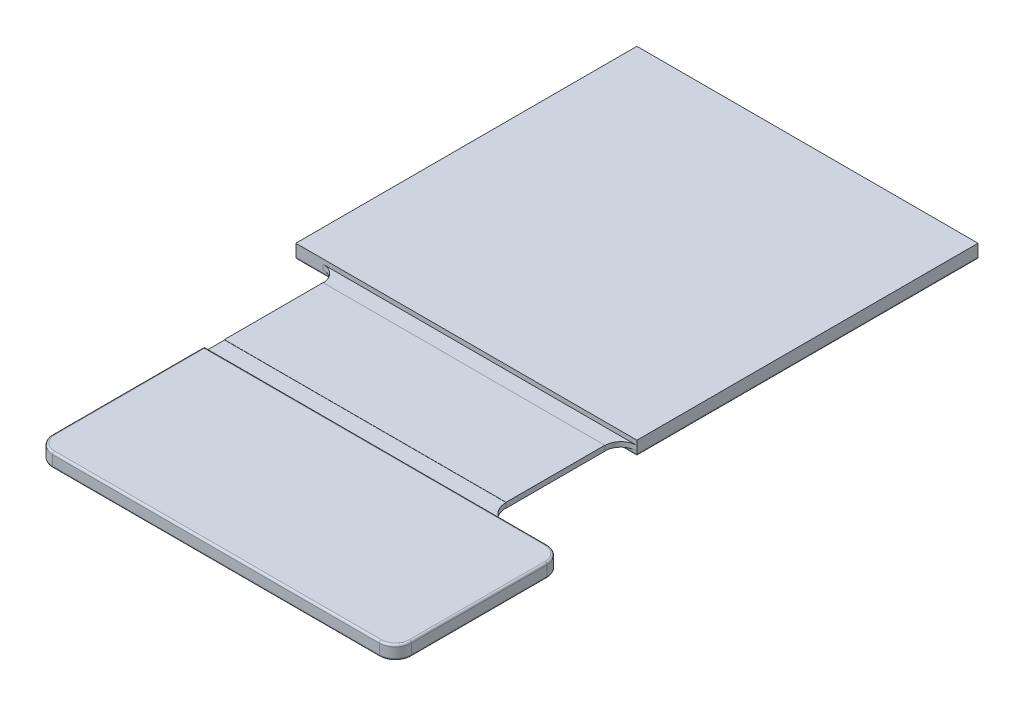
SolidWorks part; units mm, degrees
ref_plane "Front Plane" through (0, 0, 0) normal (0, 0, 1) x (1, 0, 0)
ref_plane "Top Plane" through (0, 0, 0) normal (0, 1, 0) x (1, 0, 0)
ref_plane "Right Plane" through (0, 0, 0) normal (1, 0, 0) x (0, 0, -1)
sketch "Sketch1" plane through (0, 0, 0) normal (0, 1, 0) x (1, 0, 0)
  line L1 (-4.25, 4.25) -> (4.25, 4.25) construction
  line L2 (-4.25, 4.25) -> (-4.25, -4.25) construction
  line L3 (-4.25, -4.25) -> (4.25, -4.25) construction
  line L4 (4.25, 4.25) -> (4.25, -4.25) construction
  line L5 (-4.25, 4.25) -> (4.25, -4.25) construction
  line L6 (-4.25, -4.25) -> (4.25, 4.25) construction
  line L7 (-12.5, 9.462) -> (12.5, 9.462) construction
  line L8 (-12.5, 9.462) -> (-12.5, -14.4) construction
  line L9 (-12.5, -14.4) -> (12.5, -14.4) construction
  line L10 (12.5, 9.462) -> (12.5, -14.4) construction
  line L11 (-2.27, -8.71) -> (4.87, -8.71) construction
  line L12 (-2.27, -8.71) -> (-2.27, -10.69) construction
  line L13 (-2.27, -10.69) -> (4.87, -10.69) construction
  line L14 (4.87, -8.71) -> (4.87, -10.69) construction
  line L15 (-2.27, -8.71) -> (4.87, -10.69) construction
  line L16 (-2.27, -10.69) -> (4.87, -8.71) construction
  point P0 (0, 0)
  point P10 (1.3, -9.7)
  dimension "D1" = 8.5
  dimension "D2" = 23.862
  dimension "D3" = 25
  dimension "D4" = 12.5
  dimension "D5" = 9.462
  dimension "D6" = 13.8
  dimension "D7" = 4.7
  dimension "D8" = 7.14
  dimension "D9" = 1.98
sketch "Sketch3" plane through (0, 0, 0) normal (0, 1, 0) x (1, 0, 0)
  line L0 (-4.25, 4.25) -> (4.25, 4.25) construction
  line L1 (-4.25, -4.25) -> (4.25, -4.25) construction
  line L2 (-4.25, 4.25) -> (-4.25, -4.25) construction
  line L3 (4.25, 4.25) -> (4.25, -4.25) construction
  line L4 (-4.25, -4.25) -> (-3.17, -4.25)
  line L5 (-4.25, 4.25) -> (-4.25, -4.25)
  line L6 (4.25, 4.25) -> (4.25, -4.25)
  line L7 (-4.25, 4.25) -> (4.25, 4.25)
  line L8 (4.87, -8.71) -> (4.87, -10.69) construction
  line L9 (3.85, -7.61) -> (5.77, -7.61)
  line L11 (-3.17, -11.79) -> (5.77, -11.79)
  line L12 (5.77, -7.61) -> (5.77, -11.79)
  line L13 (-2.27, -10.69) -> (4.87, -10.69) construction
  line L15 (-2.27, -8.71) -> (4.87, -8.71) construction
  line L18 (-3.17, -4.25) -> (-3.17, -11.79)
  line L19 (-2.27, -8.71) -> (-2.27, -10.69) construction
  line L20 (3.85, -4.25) -> (3.85, -7.61)
  line L21 (3.85, -4.25) -> (4.25, -4.25)
  dimension "D1" = 0.9
  dimension "D2" = 1.1
  dimension "D3" = 0.9
  dimension "D4" = 1.1
  dimension "D5" = 7.02
extrude "Boss-Extrude1" add sketch "Sketch3" along normal blind 0.35
fillet "Fillet1" radius 0.4 5 edges at (3.85, 0.175, 4.25) (-3.17, 0.175, 4.25) (5.77, 0.175, 7.61) (5.77, 0.175, 11.79) (-3.17, 0.175, 11.79)
fillet "Fillet2" radius 0.5 1 edges at (3.85, 0.175, 7.61)
sketch "Sketch4" plane through (0, 0.35, 0) normal (0, 1, 0) x (1, 0, 0)
  line L0 (-4.25, -4.25) -> (4.25, -4.25)
  line L1 (4.25, -4.25) -> (4.25, -7.61)
  line L2 (5.37, -7.61) -> (4.35, -7.61) construction
  line L3 (4.25, -7.61) -> (-4.25, -7.61)
  line L4 (-4.25, -7.61) -> (-4.25, -4.25)
extrude "Cut-Extrude1" cut sketch "Sketch4" against normal blind 0.115
sketch "Sketch5" plane through (0, 0, 0) normal (0, -1, 0) x (1, 0, 0)
  line L0 (-4.25, 7.61) -> (-4.25, 4.25) construction
  line L1 (4.25, 7.61) -> (-4.25, 7.61) construction
  line L2 (-4.25, 4.25) -> (4.25, 4.25) construction
  line L3 (4.25, 4.25) -> (4.25, 7.61) construction
  line L4 (-4.25, 7.61) -> (-4.25, 4.25)
  line L5 (4.25, 7.61) -> (-4.25, 7.61)
  line L6 (-4.25, 4.25) -> (4.25, 4.25)
  line L7 (4.25, 4.25) -> (4.25, 7.61)
extrude "Cut-Extrude2" cut sketch "Sketch5" against normal blind 0.115
fillet "Fillet3" radius 0.05 24 edges at (0, 0, -4.25) (-4.25, 0, 0) (0, 0, 4.25) (4.25, 0, 0) (-3.0528, 0, 11.6728) (1.3, 0, 11.79) (5.6528, 0, 11.6728) (5.77, 0, 9.7) (5.6528, 0, 7.7272) (4.86, 0, 7.61) (4.2997, 0, 7.6075) (4.25, 0, 7.6049) (0.54, 0, 7.61) (-3.17, 0, 9.5) (4.2997, 0.35, 7.6075) (4.86, 0.35, 7.61) (5.6528, 0.35, 7.7272) (5.77, 0.35, 9.7) (5.6528, 0.35, 11.6728) (1.3, 0.35, 11.79) (-3.0528, 0.35, 11.6728) (-3.17, 0.35, 9.5) (0.54, 0.35, 7.61) (4.25, 0.35, 7.6049)
sketch "Sketch8" plane through (0, 0.235, 0) normal (0, 1, 0) x (1, 0, 0)
  line L0 (3.85, -4.65) -> (-3.17, -4.65)
  line L1 (3.85, -4.65) -> (3.85, -7.11)
  line L2 (3.85, -7.11) -> (-3.17, -7.11)
  line L3 (-3.17, -7.61) -> (-3.17, -4.65) construction
  line L4 (-3.17, -7.11) -> (-3.17, -4.65)
extrude "Boss-Extrude2" add sketch "Sketch8" along normal blind 0.005
sketch "Sketch9" plane through (0, 0.115, 0) normal (0, -1, 0) x (1, 0, 0)
  line L4 (3.85, 4.65) -> (3.85, 7.11)
  line L5 (-3.17, 4.65) -> (3.85, 4.65)
  line L6 (-3.17, 7.11) -> (-3.17, 4.65)
  line L7 (3.85, 7.11) -> (-3.17, 7.11)
  line L8 (3.85, 4.65) -> (3.85, 7.11)
  line L9 (-3.17, 4.65) -> (3.85, 4.65)
  line L10 (-3.17, 7.11) -> (-3.17, 4.65)
  line L11 (3.85, 7.11) -> (-3.17, 7.11)
  dimension "D1" = 0
extrude "Boss-Extrude3" add sketch "Sketch9" along normal blind 0.005
sketch "Sketch10" plane through (-3.17, 0, 0) normal (-1, 0, 0) x (0, 0, 1)
  line L0 (7.11, 0.235) -> (7.11, 0.115)
  line L1 (7.11, 0.115) -> (7.61, 0.115)
  line L2 (7.61, 0.115) -> (7.61, 0.235)
  line L3 (7.61, 0.235) -> (7.11, 0.235)
extrude "Cut-Extrude3" cut sketch "Sketch10" against normal blind 0.005
